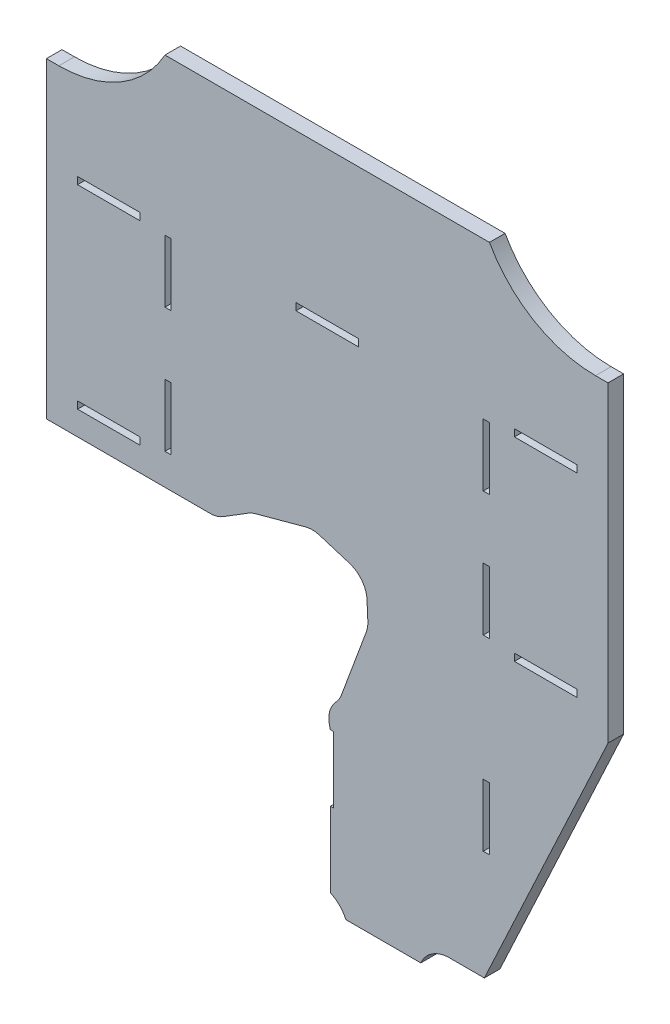
SolidWorks part; units mm, degrees
material "PBT General Purpose"
ref_plane "Front Plane" through (0, 0, 0) normal (0, 0, 1) x (1, 0, 0)
ref_plane "Top Plane" through (0, 0, 0) normal (0, 1, 0) x (1, 0, 0)
ref_plane "Right Plane" through (0, 0, 0) normal (1, 0, 0) x (0, 0, -1)
sketch "frame_outline" plane through (0, 0, 0) normal (0, 0, 1) x (1, 0, 0)
  line L0 (0, 0) -> (0, 0.3) construction
  line L1 (0, 0) -> (0.3, 0) construction
  line L2 (0, 0.3) -> (0.05, 0.3) construction
  line L3 (0.3, 0) -> (0.3, 0.05) construction
  line L4 (0.05, 0.3) -> (0.05, 1.5)
  line L5 (0.05, 1.5) -> (0.1, 1.5)
  line L6 (0.05, 0.3) -> (0.3, 0.3)
  line L7 (0.3, 0.3) -> (0.3, 0.05)
  line L8 (0.3, 0.05) -> (1.5, 0.05)
  line L9 (1.5, 0.05) -> (1.5, 0.35)
  line L10 (1.5, 0.35) -> (2.5182, 0.35)
  line L11 (2.5182, 0.35) -> (4.5, 4.6)
  line L12 (4.5, 4.6) -> (4.5, 10.6)
  line L13 (4.5, 10.6) -> (-4.5, 10.6)
  line L14 (-4.5, 10.6) -> (-4.5, 4.6)
  line L15 (-4.5, 4.6) -> (-1.7637, 4.6)
  line L16 (-1.7637, 4.6) -> (-1.2133, 4.9416)
  line L18 (0.1, 2.5625) -> (0.1, 1.5)
  line L19 (0, 10.6) -> (0, 0) construction
  line L20 (-2.5, 8.1) -> (2.5, 8.1) construction
  line L21 (-3, 5.0425) -> (3, 5.0425) construction
  line L22 (-0.5, 8.215) -> (0.5, 8.215)
  line L23 (-2.5, 8.1) -> (-2.6, 8.1)
  line L24 (-2.5, 8.1) -> (-2.5, 7.1)
  line L25 (-2.5, 7.1) -> (-2.6, 7.1)
  line L26 (-2.6, 8.1) -> (-2.6, 7.1)
  line L27 (-2.6, 6.1) -> (-2.5, 6.1)
  line L28 (-2.6, 6.1) -> (-2.6, 5.1)
  line L29 (-2.6, 5.1) -> (-2.5, 5.1)
  line L30 (-2.5, 6.1) -> (-2.5, 5.1)
  line L31 (2.5, 8.1) -> (2.6, 8.1)
  line L32 (2.5, 8.1) -> (2.5, 7.1)
  line L33 (2.5, 7.1) -> (2.6, 7.1)
  line L34 (2.6, 8.1) -> (2.6, 7.1)
  line L35 (2.5, 6.1) -> (2.6, 6.1)
  line L36 (2.5, 6.1) -> (2.5, 5.1)
  line L37 (2.5, 5.1) -> (2.6, 5.1)
  line L38 (2.6, 6.1) -> (2.6, 5.1)
  line L39 (2.5, 3.1) -> (2.6, 3.1)
  line L40 (2.5, 3.1) -> (2.5, 2.1)
  line L41 (2.5, 2.1) -> (2.6, 2.1)
  line L42 (2.6, 3.1) -> (2.6, 2.1)
  line L43 (-0.5, 8.215) -> (-0.5, 8.1)
  line L44 (-0.5, 8.1) -> (0.5, 8.1)
  line L45 (0.5, 8.215) -> (0.5, 8.1)
  line L46 (-4, 8.215) -> (-3, 8.215)
  line L47 (-4, 8.215) -> (-4, 8.1)
  line L48 (-4, 8.1) -> (-3, 8.1)
  line L49 (-3, 8.215) -> (-3, 8.1)
  line L50 (3, 8.215) -> (4, 8.215)
  line L51 (3, 8.215) -> (3, 8.1)
  line L52 (3, 8.1) -> (4, 8.1)
  line L53 (4, 8.215) -> (4, 8.1)
  line L54 (-4, 5.1) -> (-3, 5.1)
  line L55 (-4, 5.1) -> (-4, 4.985)
  line L56 (-4, 4.985) -> (-3, 4.985)
  line L57 (-3, 5.1) -> (-3, 4.985)
  line L58 (3, 5.1) -> (4, 5.1)
  line L59 (3, 5.1) -> (3, 4.985)
  line L60 (3, 4.985) -> (4, 4.985)
  line L61 (4, 5.1) -> (4, 4.985)
  line L62 (-3, 8.1575) -> (3, 8.1575) construction
  line L63 (0.1, 2.5625) -> (0.05, 2.5625)
  line L64 (0.05, 2.5625) -> (-0.0089, 2.8119)
  line L65 (-0.0089, 2.8119) -> (0.2035, 3.0663)
  line L66 (0.2035, 3.0663) -> (0.655, 4.2832)
  line L67 (0.655, 4.2832) -> (0.6251, 4.9416)
  line L68 (0.6251, 4.9416) -> (-0.2329, 5.2084)
  line L69 (-0.2329, 5.2084) -> (-1.2133, 4.9416)
  line L71 (-0.5, 4.985) -> (0.5, 4.985) construction
  line L72 (-0.5, 4.985) -> (-0.5, 5.1) construction
  line L73 (-0.5, 5.1) -> (0.5, 5.1) construction
  line L74 (0.5, 4.985) -> (0.5, 5.1) construction
  point P40 (0, 8.1)
  point P53 (0, 8.215)
  point P64 (0, 5.0425)
  point P65 (0, 8.1575)
  point P87 (2.55, 2.1)
  dimension "D2" = 0.3
  dimension "D3" = 0.05
  dimension "D4" = 0.05
  dimension "D5" = 1.2
  dimension "D6" = 1.2
  dimension "D7" = 0.05
  dimension "D8" = 0.3
  dimension "D10" = 9
  dimension "D13" = 6
  dimension "D14" = 10.6
  dimension "D15" = 6
  dimension "D16" = 5
  dimension "D17" = 0.1
  dimension "D18" = 0.1
  dimension "D19" = 1
  dimension "D20" = 1
  dimension "D21" = 1
  dimension "D22" = 2.5
  dimension "D23" = 1
  dimension "D24" = 0.115
  dimension "D25" = 1
  dimension "D26" = 1
  dimension "D27" = 0.115
  dimension "D28" = 3
  dimension "D29" = 3
  dimension "D30" = 2
  dimension "D9" = 155
  dimension "D11" = 0.0318
extrude "Boss-Extrude1" add sketch "frame_outline" along normal mid plane 0.25
fillet "Fillet1" radius 0.5 2 edges at (1.5, 0.35, 0) (0.3, 0.3, 0)
fillet "Fillet2" radius 0.4 7 edges at (-1.7637, 4.6, 0) (-1.2133, 4.9416, 0) (-0.2329, 5.2084, 0) (0.6251, 4.9416, 0) (0.655, 4.2832, 0) (0.2035, 3.0663, 0) (-0.0089, 2.8119, 0)
sketch "Sketch1" plane through (0, 0, 0.125) normal (0, 0, 1) x (1, 0, 0)
  line L0 (-4.5, 9.6) -> (-4.5, 10.6)
  line L1 (-4.5, 10.6) -> (-4.5, 4.6) construction
  line L2 (-4.5, 10.6) -> (-2.6, 10.6)
  line L3 (4.5, 10.6) -> (-4.5, 10.6) construction
  line L6 (-4.3, 9.6) -> (-4.5, 9.6)
  line L7 (4.5, 10.6) -> (4.5, 9.6)
  line L8 (4.5, 4.6) -> (4.5, 10.6) construction
  line L9 (4.5, 9.6) -> (4.3, 9.6)
  line L12 (2.6, 10.6) -> (4.5, 10.6)
  arc A0 (-4.3, 9.6) -> (-2.6, 10.6) centre (-4.3, 11.545) ccw
  arc A1 (4.3, 9.6) -> (2.6, 10.6) centre (4.3, 11.545) cw
  dimension "D1" = 1
  dimension "D2" = 1
  dimension "D3" = 1.9
  dimension "D4" = 1.9
  dimension "D5" = 0.2
  dimension "D6" = 0.2
extrude "Cut-Extrude1" cut sketch "Sketch1" against normal through all
equation "\"t\"= 0.25'thickness of the sheets"
equation "\"t_cf\" = 0.115'thickness of single carbon fiber layer"
equation "\"t_kapton\" = 0.025'thickness of single Kapton flex layer"
equation "\"t_fr4\" = 0.1'thickness of FR4 with copper layer"
equation "\"joint_flex\"= 0.1'Width of flextures gap"
equation "\"joint_flex_eff\"= 0.02'Width of flecture after castelation"
equation "\"joint_fold\"= 0.2'Width of folding joints for 90deg fold"
equation "\"gap_tolerance\"= 0.002'Width to have interfecence fit between carbon fiber inserts"
equation "\"assemble_angle\"= 90'Angle of assembly parts"
equation "\"D3@frame_outline\" = \"joint_flex\" / 2"
equation "\"D4@frame_outline\" = \"joint_flex\" / 2"
equation "\"D17@frame_outline\" = \"t_fr4\""
equation "\"D18@frame_outline\" = \"t_fr4\""
equation "\"D24@frame_outline\" = \"t_cf\""
equation "\"D27@frame_outline\" = \"t_cf\""
equation "\"D1@Boss-Extrude1\"=\"t\""
equation "\"link_lift\"= 0.5'Actuation linkage amplification for the lift motion"
equation "\"link_swing\"= 0.45'Actuation linkage amplification for the swing motion"
